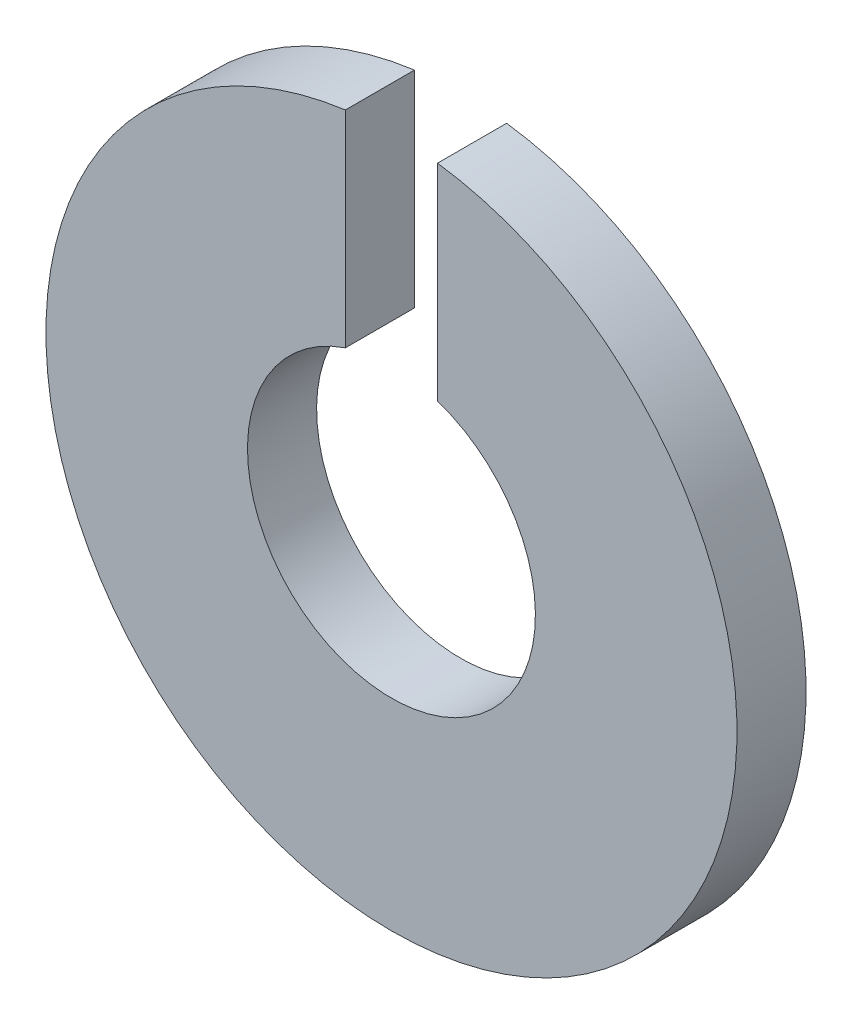
SolidWorks part; units mm, degrees
ref_plane "Front Plane" through (0, 0, 0) normal (0, 0, 1) x (1, 0, 0)
ref_plane "Top Plane" through (0, 0, 0) normal (0, 1, 0) x (1, 0, 0)
ref_plane "Right Plane" through (0, 0, 0) normal (1, 0, 0) x (0, 0, -1)
sketch "Sketch1" plane through (0, 0, 0) normal (0, 0, 1) x (1, 0, 0)
  circle A0 centre (0, 0) radius 30
  circle A1 centre (0, 0) radius 12.5
  dimension "OD" = 60
  dimension "ID1" = 25
extrude "Boss-Extrude1" add sketch "Sketch1" along normal blind 6
ref_axis "Center Axis 1" through (0, 0, 6) along (0, 0, -1)
ref_plane "Contact Plane 1" through (0, 0, 6) normal (0, 0, 1) x (1, 0, 0)
ref_plane "Contact Plane 2" through (0, 0, 0) normal (0, 0, -1) x (-1, 0, 0)
sketch "Sketch2" plane through (0, 0, 6) normal (0, 0, 1) x (1, 0, 0)
  line L1 (-4, 0) -> (4, 0)
  line L2 (-4, 0) -> (-4, 40)
  line L3 (-4, 40) -> (4, 40)
  line L4 (4, 0) -> (4, 40)
  point P4 (0, 0)
  dimension "D1" = 8
  dimension "D2" = 40
extrude "Cut-Extrude1" cut sketch "Sketch2" against normal through all both
